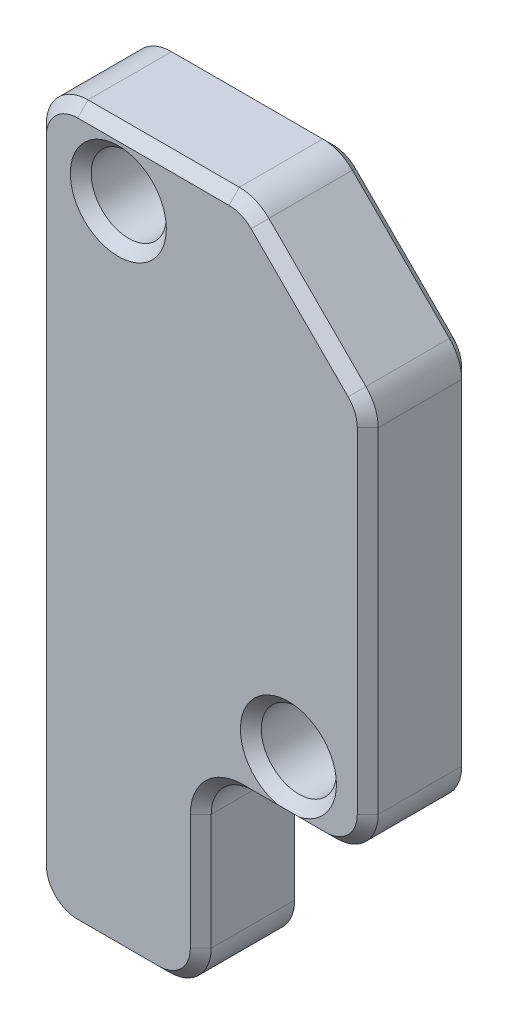
SolidWorks part; units mm, degrees
ref_plane "Front" through (0, 0, 0) normal (0, 0, 1) x (1, 0, 0)
ref_plane "Top" through (0, 0, 0) normal (0, 1, 0) x (1, 0, 0)
ref_plane "Right" through (0, 0, 0) normal (1, 0, 0) x (0, 0, -1)
sketch "Skizze1" plane through (0, 0, 0) normal (0, 0, 1) x (1, 0, 0)
  line L4 (-0.2, 9.7513) -> (-0.2, 28.6272)
  line L5 (0, 27.8817) -> (0, 11.5513) construction
  line L6 (-6.0228, 34.45) -> (-0.2, 28.6272)
  line L7 (-5.3541, 34.0642) -> (-0.5858, 29.2959) construction
  line L8 (-16.1, 34.45) -> (-6.0228, 34.45)
  line L9 (-14.3, 34.65) -> (-6.7683, 34.65) construction
  line L10 (-16.1, 0.2) -> (-16.1, 34.45)
  line L11 (-16.3, 0) -> (-16.3, 32.65) construction
  line L12 (-8.2, 9.7513) -> (-0.2, 9.7513)
  line L13 (-2, 9.5513) -> (-6, 9.5513) construction
  line L14 (-16.1, 0.2) -> (-8.2, 0.2)
  line L15 (-8.2, 0.2) -> (-8.2, 9.7513)
  line L16 (-8, 7.5513) -> (-8, 0) construction
  line L17 (-8, 0) -> (-16.3, 0) construction
  circle A0 centre (-12.15, 31.475) radius 1.8
  circle A1 centre (-4, 12.4911) radius 1.8
  dimension "D8" = 3.6
  dimension "D1" = 0.2
  dimension "D2" = 0.2
  dimension "D3" = 0.2
  dimension "D4" = 0.2
  dimension "D5" = 0.2
  dimension "D6" = 0.2
  dimension "D7" = 0.2
extrude "Aufsatz-Linear austragen1" add sketch "Skizze1" along normal blind 5
fillet "Verrundung1" radius 2 7 edges at (-0.2, 9.7513, 2.5) (-8.2, 9.7513, 2.5) (-8.2, 0.2, 2.5) (-16.1, 0.2, 2.5) (-16.1, 34.45, 2.5) (-6.0228, 34.45, 2.5) (-0.2, 28.6272, 2.5)
chamfer "Fase1" distance 0.5 angle 45 32 edges at (-2.2, 12.4911, 0) (-10.35, 31.475, 0) (-0.3522, 28.5642, 0) (-3.1114, 31.5386, 0) (-6.0858, 34.2978, 0) (-10.4756, 34.45, 0) (-15.5142, 33.8642, 0) (-16.1, 17.325, 0) (-15.5142, 0.7858, 0) (-12.15, 0.2, 0) (-8.7858, 0.7858, 0) (-8.2, 4.9757, 0) (-7.6142, 9.1656, 0) (-4.2, 9.7513, 0) (-0.7858, 10.3371, 0) (-0.2, 19.7751, 0) (-2.2, 12.4911, 5) (-7.6142, 9.1656, 5) (-8.2, 4.9757, 5) (-8.7858, 0.7858, 5) (-12.15, 0.2, 5) (-15.5142, 0.7858, 5) (-16.1, 17.325, 5) (-15.5142, 33.8642, 5) (-10.4756, 34.45, 5) (-6.0858, 34.2978, 5) (-3.1114, 31.5386, 5) (-0.3522, 28.5642, 5) (-0.2, 19.7751, 5) (-0.7858, 10.3371, 5) (-4.2, 9.7513, 5) (-10.35, 31.475, 5)
